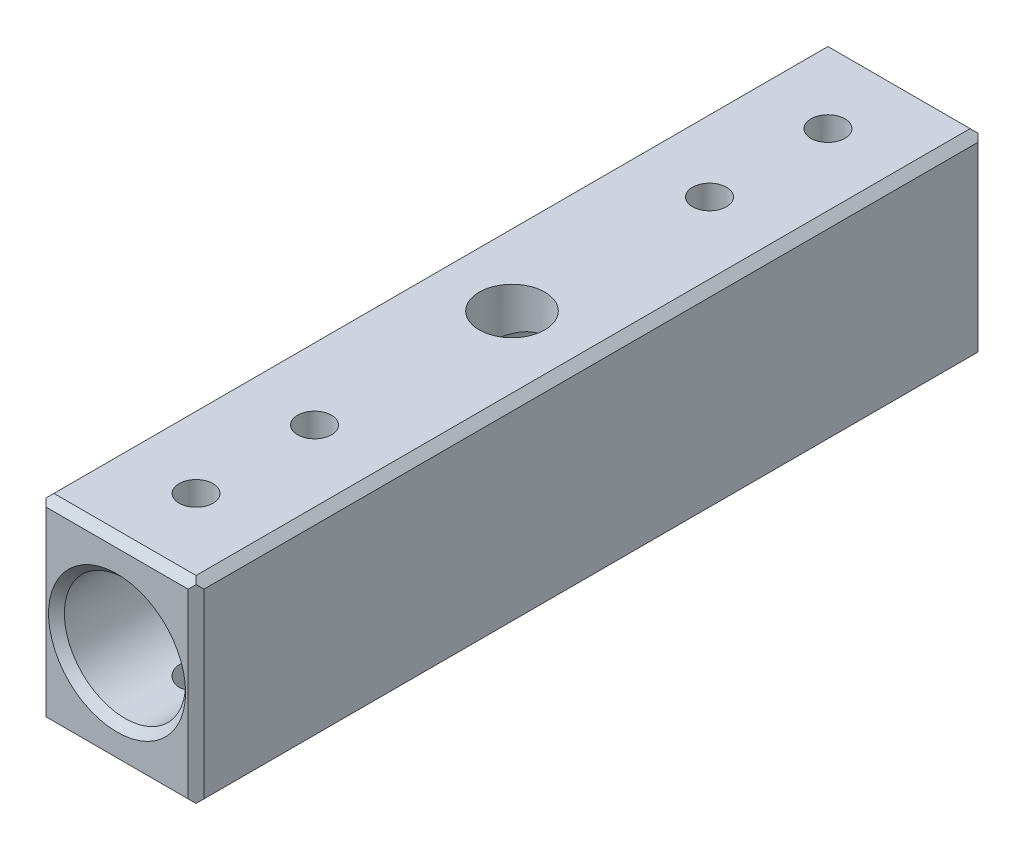
SolidWorks part; units mm, degrees
material "ABS"
ref_plane "前视基准面" through (0, 0, 0) normal (0, 0, 1) x (1, 0, 0)
ref_plane "上视基准面" through (0, 0, 0) normal (0, 1, 0) x (1, 0, 0)
ref_plane "右视基准面" through (0, 0, 0) normal (1, 0, 0) x (0, 0, -1)
other "Configuration Table"
sketch "草图2" plane through (0, 0, 0) normal (0, 0, 1) x (1, 0, 0)
  line L11 (-10, 12.5) -> (10, 12.5)
  line L12 (-10, 12.5) -> (-10, -12.5)
  line L13 (-10, -12.5) -> (10, -12.5)
  line L14 (10, 12.5) -> (10, -12.5)
  line L15 (0, -12.5) -> (0, 12.5) construction
  line L16 (-10, 0) -> (10, 0) construction
  circle A0 centre (0, 0) radius 7.675
  point P0 (0, 0)
  dimension "D1" = 15.35
  dimension "D4" = 25
  dimension "D5" = 20
extrude "凸台-拉伸1" add sketch "草图2" against normal blind 100
sketch "草图3" plane through (0, 12.5, 0) normal (0, 1, 0) x (1, 0, 0)
  line L0 (0, 100) -> (0, 0) construction
  line L1 (0, 25) -> (0, 75) construction
  line L2 (-10, 50) -> (10, 50) construction
  line L4 (-10, 0) -> (10, 0)
  line L5 (10, 0) -> (10, 100)
  line L6 (10, 100) -> (-10, 100)
  line L7 (-10, 100) -> (-10, 0)
  line L8 (-10, 0) -> (10, 0)
  line L9 (10, 0) -> (10, 100)
  line L10 (10, 100) -> (-10, 100)
  line L11 (-10, 100) -> (-10, 0)
  circle A0 centre (0, 75) radius 2.15
  circle A2 centre (0, 50) radius 4.15
  circle A3 centre (0, 90) radius 2.15
  circle A4 centre (0, 10) radius 2.15
  circle A5 centre (0, 25) radius 2.15
  point P10 (0, 50)
  dimension "D2" = 4.3
  dimension "D3" = 15
  dimension "D5" = 8.3
  dimension "D4" = 25
  dimension "D1" = 0
extrude "切除-拉伸2" cut sketch "草图3" against normal through all contours A2 | A0 | A3 | A5 | A4 region at (0, 12.5, -75) region at (0, 12.5, -50) region at (0, 12.5, -90) region at (0, 12.5, -10) region at (0, 12.5, -25)
sketch "草图5" plane through (10, 0, 0) normal (1, 0, 0) x (0, 0, -1)
  line L0 (0, 0) -> (100, 0) construction
  line L1 (0, -12.5) -> (0, 12.5) construction
  line L2 (100, -12.5) -> (100, 12.5) construction
  line L3 (50, 12.5) -> (50, -12.5) construction
  line L4 (100, 12.5) -> (0, 12.5) construction
  line L5 (100, -12.5) -> (0, -12.5) construction
  circle A0 centre (10, 0) radius 2.15
  circle A1 centre (90, 0) radius 2.15
  dimension "D1" = 4.3
  dimension "D2" = 10
chamfer "倒角1" distance 1 angle 45 10 edges at (0, 12.5, -100) (-10, 0, -100) (0, -12.5, -100) (10, 0, -100) (0, -12.5, 0) (-10, 0, 0) (0, 12.5, 0) (10, 0, 0) (7.675, 0, -100) (7.675, 0, 0)
chamfer "倒角2" distance 1 angle 45 4 edges at (10, -12.5, -50) (-10, -12.5, -50) (10, 12.5, -50) (-10, 12.5, -50)
